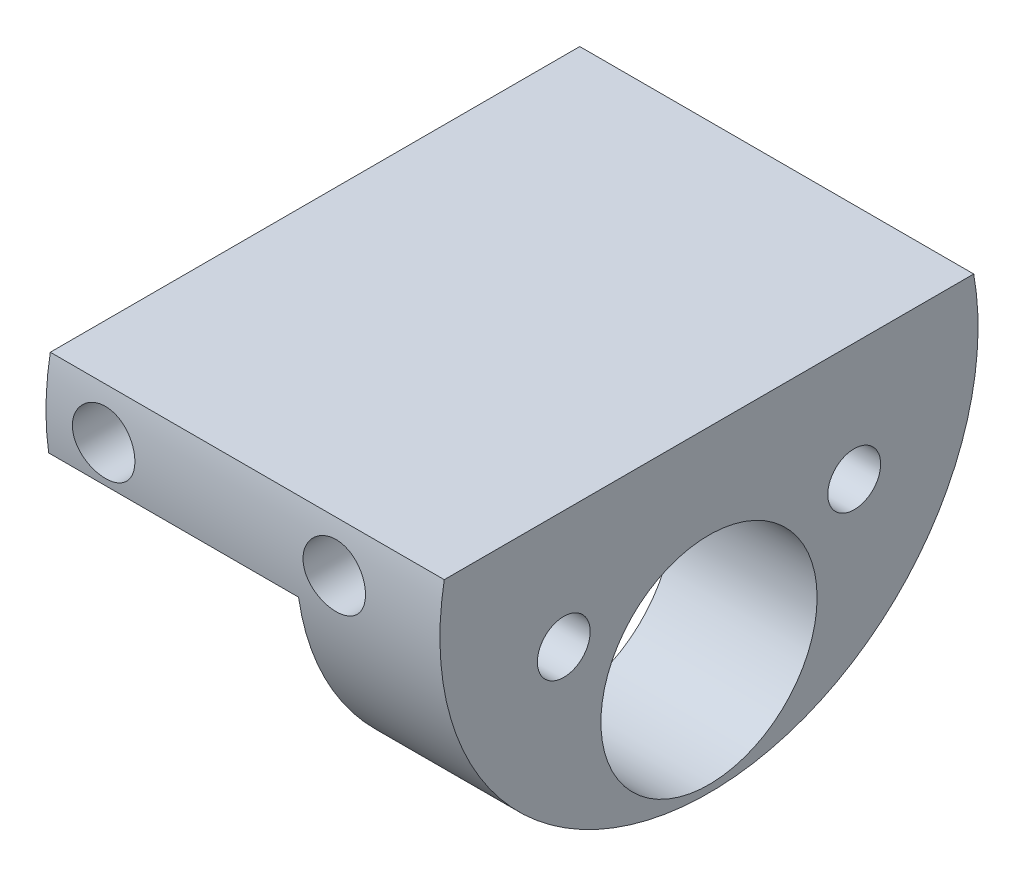
SolidWorks part; units mm, degrees
ref_plane "Front Plane" through (0, 0, 0) normal (0, 0, 1) x (1, 0, 0)
ref_plane "Top Plane" through (0, 0, 0) normal (0, 1, 0) x (1, 0, 0)
ref_plane "Right Plane" through (0, 0, 0) normal (1, 0, 0) x (0, 0, -1)
sketch "Sketch1" plane through (0, 0, 0) normal (0, 0, 1) x (1, 0, 0)
  line L0 (0, 0) -> (-18.1432, 0) construction
  circle A0 centre (0, 0) radius 3.25
  circle A1 centre (24, 0) radius 3.25
  dimension "D2" = 6.5
  dimension "D1" = 24
sketch "Sketch2" plane through (0, 0, 0) normal (1, 0, 0) x (0, 0, -1)
  line L0 (0, 0) -> (0, 28) construction
  line L1 (-27.55, 5) -> (27.55, 5)
  line L2 (0, 0) -> (0, -16) construction
  line L3 (-15.1121, -7.275) -> (0, -16) construction
  line L4 (0, -16) -> (15.1121, -7.275) construction
  line L5 (-27.7128, -4) -> (27.7128, -4)
  circle A0 centre (0, 0) radius 28
  circle A1 centre (0, -16) radius 11.25
  circle A2 centre (0, -16) radius 17.45 construction
  circle A3 centre (-15.1121, -7.275) radius 2.75
  circle A5 centre (15.1121, -7.275) radius 2.75
  circle A6 centre (15.1121, -7.275) radius 4
  circle A7 centre (-15.1121, -7.275) radius 4
  dimension "D1" = 56
  dimension "D3" = 22.5
  dimension "D4" = 34.9
  dimension "D5" = 5.5
  dimension "D8" = 5.5
  dimension "D11" = 8
  dimension "D12" = 8
  dimension "D2" = 5
  dimension "D6" = 16
  dimension "D7" = 60
  dimension "D9" = 60
  dimension "D10" = 4
extrude "Boss-Extrude1" add sketch "Sketch2" along normal blind 20 and the other way blind 6 contours L1 A0 L5 region at (0, 0.5339, 0)
extrude "Boss-Extrude2" add sketch "Sketch2<4>" along normal blind 15 from surface contours L5 A0 A5 A3 A1 | L1 A0 L5 | L5 A7 A3 | L5 A6 A5 | L5 A7 | L5 A6 region at (0, 0.5339, 0) region at (0, -4.604, 22.5608) region at (0, -3.7076, 15.1121) region at (0, -4.1081, 15.1121) region at (0, -5.4791, -18.5649) region at (0, -3.7076, -15.1121) starting at face at (20, -1.5671, 0)
sketch "Sketch2<4>" plane through (0, 0, 0) normal (1, 0, 0) x (0, 0, -1) same geometry as "Sketch2"
extrude "Cut-Extrude1" cut sketch "Sketch1" against normal through all and the other way through all
